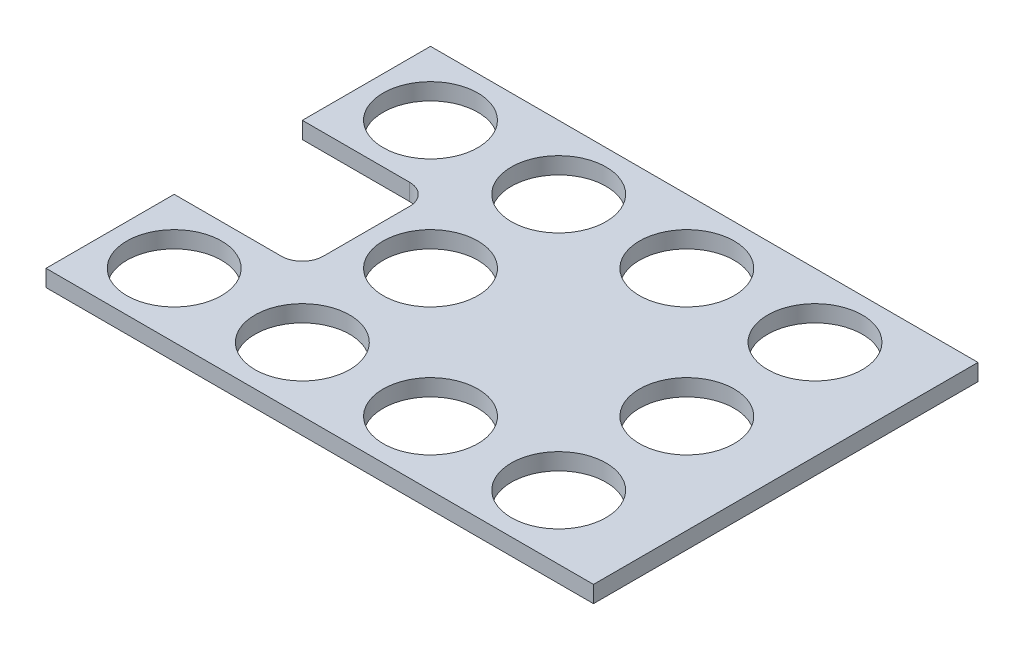
SolidWorks part; units mm, degrees
material "Pine"
ref_plane "Front Plane" through (0, 0, 0) normal (0, 0, 1) x (1, 0, 0)
ref_plane "Top Plane" through (0, 0, 0) normal (0, 1, 0) x (1, 0, 0)
ref_plane "Right Plane" through (0, 0, 0) normal (1, 0, 0) x (0, 0, -1)
sketch "Sketch1" plane through (0, 0, 0) normal (0, 1, 0) x (1, 0, 0)
  line L0 (46, 46) -> (264.076, 46)
  line L1 (0, 0) -> (393, 0)
  line L2 (0, 0) -> (0, 276)
  line L3 (0, 276) -> (393, 276)
  line L4 (393, 0) -> (393, 276)
  line L6 (0, 184) -> (77, 184)
  line L7 (0, 184) -> (0, 92)
  line L8 (0, 92) -> (77, 92)
  line L9 (92, 169) -> (92, 107)
  circle A0 centre (46, 46) radius 34
  circle A1 centre (46, 230) radius 34
  arc A2 (77, 92) -> (92, 107) centre (77, 107) ccw
  arc A3 (77, 184) -> (92, 169) centre (77, 169) cw
  circle A4 centre (138, 138) radius 34
  circle A5 centre (322, 138) radius 34
  dimension "D2" = 68
  dimension "D9" = 15
  dimension "D1" = 46
  dimension "D4" = 276
  dimension "D5" = 46
  dimension "D6" = 46
  dimension "D7" = 46
  dimension "D8" = 92
  dimension "D10" = 92
  dimension "D11" = 92
  dimension "D12" = 138
  dimension "D13" = 138
  dimension "D14" = 184
  dimension "D15" = 138
  dimension "D3" = 393
extrude "Boss-Extrude1" add sketch "Sketch1" along normal blind 12 contours L2 L3 L4 L1
extrude "Cut-Extrude1" cut sketch "Sketch1<3>" along normal up to surface (12 mm away) contours A0 | A1 up to face at (196.5, 12, -138)
sketch "Sketch1<3>" plane through (0, 0, 0) normal (0, 1, 0) x (1, 0, 0) same geometry as "Sketch1"
pattern_linear "LPattern1" count 4 spacing 92 along (1, 0, 0) of "Cut-Extrude1"
extrude "Cut-Extrude3" cut sketch "Sketch1<4>" along normal up to surface (12 mm away) contours A3 L6 L2 L8 A2 L9 | A4 | A5 region at (45.5078, 0, -138) region at (138, 0, -138) region at (322, 0, -138) up to face at (322, 12, -12)
sketch "Sketch1<4>" plane through (0, 0, 0) normal (0, 1, 0) x (1, 0, 0) same geometry as "Sketch1"
equation "\"LENGTH\" = 900mm"
equation "\"PLY\"= 12mm"
equation "\"D1@Boss-Extrude1\"=\"PLY\""
equation "\"CENTER_BRACE_LENGTH\" = 393mm"
equation "\"D3@Sketch1\"=\"CENTER_BRACE_LENGTH\""
